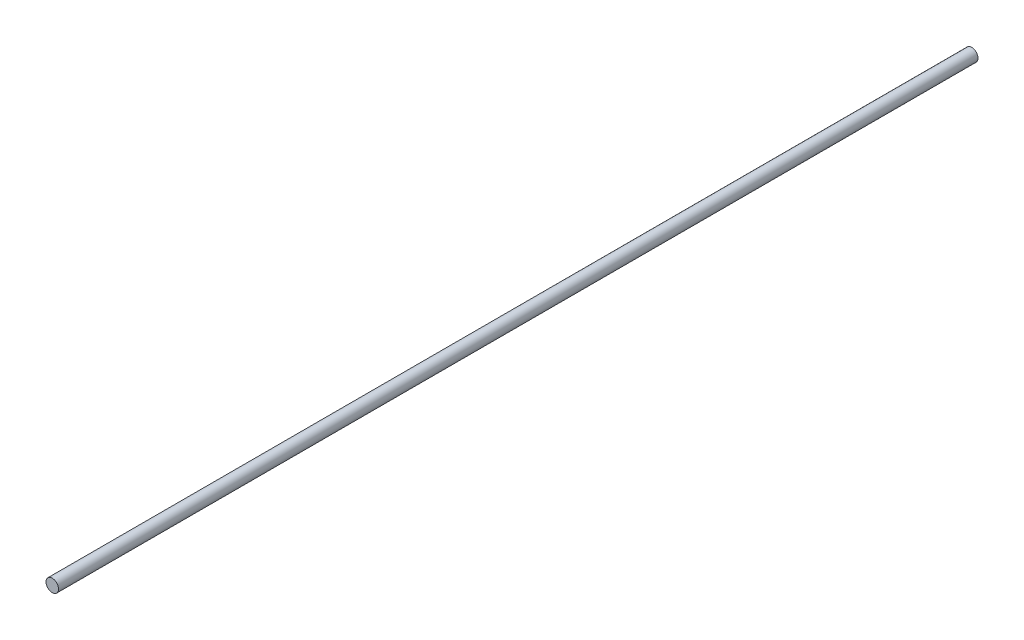
SolidWorks part; units mm, degrees
ref_plane "Front Plane" through (0, 0, 0) normal (0, 0, 1) x (1, 0, 0)
ref_plane "Top Plane" through (0, 0, 0) normal (0, 1, 0) x (1, 0, 0)
ref_plane "Right Plane" through (0, 0, 0) normal (1, 0, 0) x (0, 0, -1)
sketch "Sketch1" plane through (0, 0, 0) normal (0, 0, 1) x (1, 0, 0)
  circle A0 centre (0, 0) radius 1.5
  dimension "D1" = 3
extrude "Boss-Extrude1" add sketch "Sketch1" along normal blind 110 and the other way blind 110
